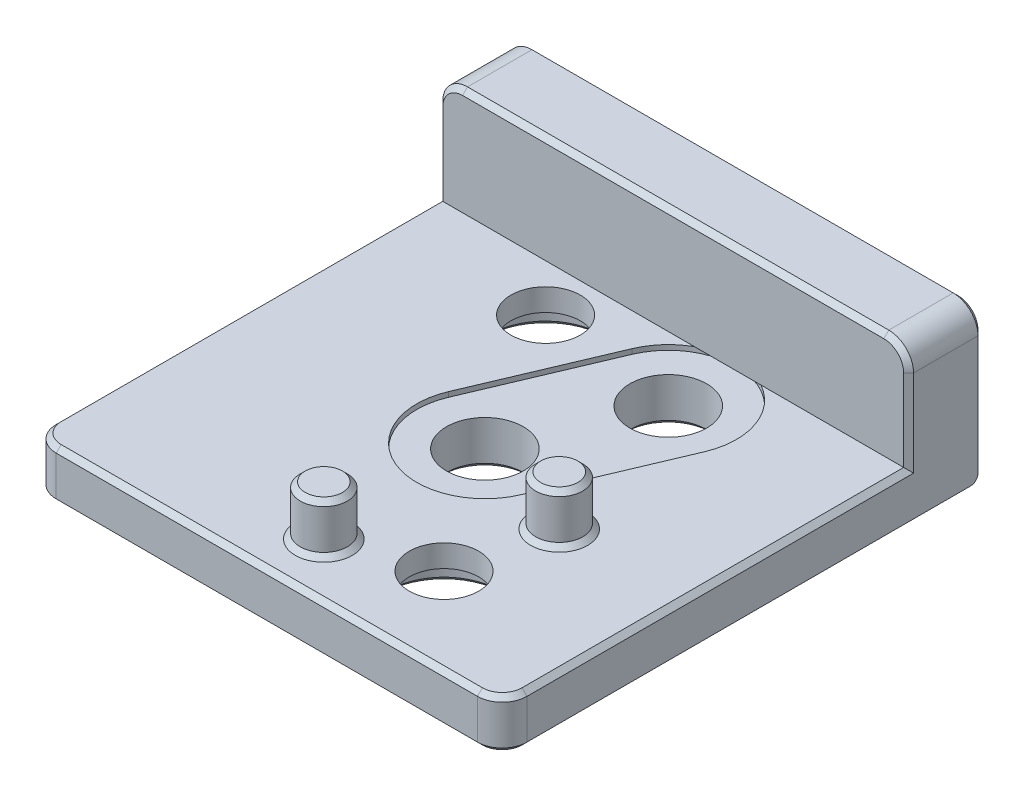
SolidWorks part; units mm, degrees
ref_plane "Front Plane" through (0, 0, 0) normal (0, 0, 1) x (1, 0, 0)
ref_plane "Top Plane" through (0, 0, 0) normal (0, 1, 0) x (1, 0, 0)
ref_plane "Right Plane" through (0, 0, 0) normal (1, 0, 0) x (0, 0, -1)
sketch "Sketch1" plane through (0, 0, 0) normal (1, 0, 0) x (0, 0, -1)
  line L1 (0, 0) -> (19.4, 0)
  line L2 (0, 0) -> (0, -2)
  line L3 (0, -2) -> (19.4, -2)
  line L4 (19.4, 0) -> (19.4, -2)
  line L5 (19.4, 0) -> (16.4, 0)
  line L6 (19.4, 0) -> (19.4, 4.3)
  line L7 (19.4, 4.3) -> (16.4, 4.3)
  line L8 (16.4, 0) -> (16.4, 4.3)
  dimension "D1" = 2
  dimension "D2" = 3
  dimension "D3" = 16.4
  dimension "D4" = 6.3
extrude "Boss-Extrude1" add sketch "Sketch1" along normal mid plane 19 contours L4 L1 L2 L3 | L8 L1 L6 L7 region at (0, -1, -9.7) region at (0, 2.15, -17.9)
sketch "Sketch2" plane through (0, 0, 0) normal (0, 1, 0) x (1, 0, 0)
  line L0 (0, 0) -> (0, 8.8)
  line L1 (9.5, 0) -> (-9.5, 0) construction
  line L2 (9.5, 0) -> (9.5, 16.4) construction
  circle A0 centre (0, 8.8) radius 1.55
  circle A1 centre (2.2, 14) radius 1.55
  circle A2 centre (3.65, 3.5) radius 1.4
  circle A3 centre (-3.25, 14.5) radius 1.4
  dimension "D2" = 3.1
  dimension "D5" = 2.8
  dimension "D1" = 8.8
  dimension "D3" = 14
  dimension "D4" = 7.3
  dimension "D6" = 12.75
  dimension "D7" = 14.5
  dimension "D8" = 5.85
  dimension "D9" = 3.5
extrude "Cut-Extrude1" cut sketch "Sketch2" against normal through all contours A0 | A1 | A3 | A2 region at (1.065, 0, -7.735) region at (2.2, 0, -14) region at (3.65, 0, -3.5) region at (-3.25, 0, -14.5)
sketch "Sketch3" plane through (0, 0, 0) normal (0, 1, 0) x (1, 0, 0)
  line L0 (0, 8.8) -> (2.2, 14) construction
  line L1 (-2.5327, 9.8715) -> (-0.3327, 15.0715)
  line L2 (2.5327, 7.7285) -> (4.7327, 12.9285)
  arc A0 (-2.5327, 9.8715) -> (2.5327, 7.7285) centre (0, 8.8) ccw
  arc A1 (4.7327, 12.9285) -> (-0.3327, 15.0715) centre (2.2, 14) ccw
  circle A2 centre (2.2, 14) radius 1.55 construction
  circle A3 centre (0, 8.8) radius 1.55 construction
  point P2 (1.1, 11.4)
  dimension "D1" = 2.75
extrude "Cut-Extrude2" cut sketch "Sketch3" against normal blind 0.2
sketch "Sketch4" plane through (0, -2, 0) normal (0, -1, 0) x (1, 0, 0)
  circle A0 centre (-3.25, -14.5) radius 2.25
  circle A1 centre (3.65, -3.5) radius 2.25
  circle A2 centre (-3.25, -14.5) radius 1.4 construction
  circle A3 centre (3.65, -3.5) radius 1.4 construction
  dimension "D1" = 4.5
extrude "Cut-Extrude3" cut sketch "Sketch4" against normal blind 1.1
fillet "Fillet1" radius 1 4 edges at (-9.5, 4.3, -17.9) (9.5, 4.3, -17.9) (-9.5, -1, 0) (9.5, -1, 0)
sketch "Sketch5" plane through (0, 0, 0) normal (0, 1, 0) x (1, 0, 0)
  line L0 (9.5, 1) -> (9.5, 16.4) construction
  line L1 (8.5, 0) -> (-8.5, 0) construction
  circle A0 centre (0.1, 2.2) radius 0.95
  circle A1 centre (4.5, 7.3) radius 0.95
  dimension "D1" = 1.9
  dimension "D2" = 5
  dimension "D3" = 9.4
  dimension "D4" = 2.2
  dimension "D5" = 7.3
extrude "Boss-Extrude2" add sketch "Sketch5" along normal blind 2
fillet "Fillet4" radius 0.5 1 edges at (0, -2, -19.4)
chamfer "Chamfer1" distance 0.2 angle 45 30 edges at (9.5, 1.65, -16.4) (9.2071, 4.0071, -16.4) (0, 4.3, -16.4) (-9.5, 1.65, -16.4) (-9.2071, 4.0071, -16.4) (9.5, -2, -9.95) (9.5, -1.8536, -19.2536) (9.2071, -2, -0.2929) (9.5, 0.9, -19.4) (0, -2, 0) (9.2071, 4.0071, -19.4) (-9.2071, -2, -0.2929) (0, 4.3, -19.4) (-9.5, -2, -9.95) (-9.2071, 4.0071, -19.4) (-9.5, -1.8536, -19.2536) (-9.5, 0.9, -19.4) (9.5, 0, -8.7) (9.2071, 0, -0.2929) (0, 0, 0) (-9.2071, 0, -0.2929) (-9.5, 0, -8.7) (0.1, 0, -1.25) (0.1, 2, -1.25) (4.5, 0, -6.35) (4.5, 2, -6.35) (0, -2, -7.25) (2.2, -2, -12.45) (3.65, -2, -5.75) (-3.25, -2, -16.75)
